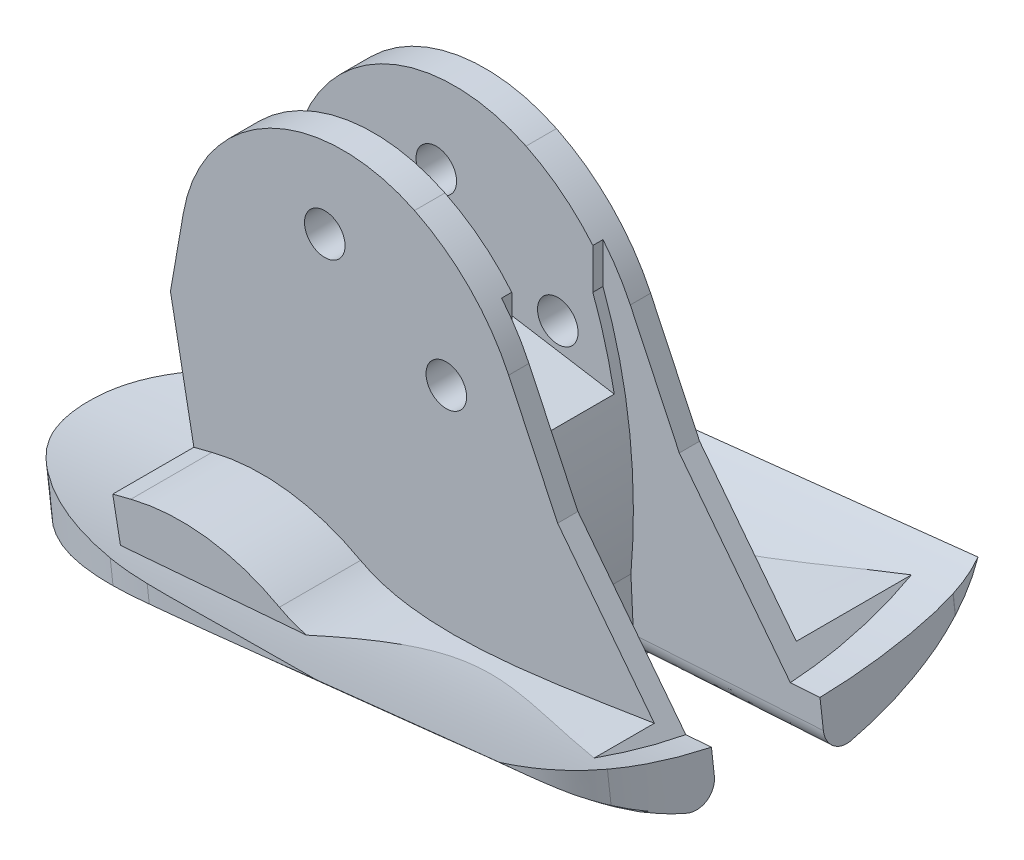
SolidWorks part; units mm, degrees
ref_plane "Спереди" through (0, 0, 0) normal (0, 0, 1) x (1, 0, 0)
ref_plane "Сверху" through (0, 0, 0) normal (0, 1, 0) x (1, 0, 0)
ref_plane "Справа" through (0, 0, 0) normal (1, 0, 0) x (0, 0, -1)
sketch "Sketch5" plane through (0, 0, 0) normal (0, 0, 1) x (1, 0, 0)
  line L0 (1.7523, 0.4742) -> (37.3029, 86.8114) construction
  line L1 (-1.0106, -0.6044) -> (29.6618, 87.5839) construction
  line L2 (0, 0) -> (17.8901, 43.1295)
  line L3 (0, 0) -> (114.3643, 0) construction
  line L4 (23.8823, 39.6684) -> (24.5035, 51.2503)
  line B0 (17.4507, 115.16) -> (29.9551, 112.6983)
  spline B1 degree 3 poles (29.9551, 112.6983) (28.321, 116.0983) (27.9284, 121.1676) (30.1713, 134.4746) (29.8473, 132.0116) (30.6222, 139.9349) (27.0176, 140.9027) knots 0 0 0 0 0.297085 0.369784 0.687298 1 1 1 1
  spline B2 degree 2 poles (27.0176, 140.9027) (20.5603, 128.6427) (17.4507, 115.16) knots 0 0 0 1 1 1
  spline B3 degree 2 poles (27.0176, 140.9027) (26.5004, 134.6878) (22.2537, 130.5645) knots 0 0 0 1 1 1
  line B4 (17.1977, 114.3508) -> (29.842, 112.2111)
  line B5 (28.7001, 84.8969) -> (10.3668, 87.513)
  spline B6 degree 1 poles (17.1977, 114.3508) (10.3668, 87.513) knots 0 0 1 1
  spline B7 degree 2 poles (29.842, 112.2111) (22.5534, 98.8452) (28.7001, 84.8969) knots 0 0 0 1 1 1
  line B8 (10.1904, 87.4159) -> (28.2572, 84.4958)
  line B9 (32.8909, 45.7292) -> (10.0695, 42.8593)
  spline B10 degree 2 poles (10.1904, 87.4159) (10.0234, 65.1379) (10.0695, 42.8593) knots 0 0 0 1 1 1
  spline B11 degree 2 poles (28.2572, 84.4958) (20.6417, 64.1094) (32.8909, 45.7292) knots 0 0 0 1 1 1
  line B12 (10.2797, 36.8758) -> (3.9253, -13.9853)
  line B13 (3.9253, -13.9853) -> (33.9594, -31.0804)
  line B14 (33.9594, -31.0804) -> (45.9193, -27.7969)
  line B15 (45.9193, -27.7969) -> (58.2918, -13.9853)
  line B16 (58.2918, -13.9853) -> (69.0331, -4.9875)
  line B17 (69.0331, -4.9875) -> (82.514, 2.0236)
  line B18 (82.514, 2.0236) -> (89.2736, 3.8794)
  line B19 (89.2736, 3.8794) -> (92.4846, 9.5208)
  line B20 (92.4846, 9.5208) -> (96.8914, 17.263)
  line B21 (96.8914, 17.263) -> (101.4978, 21.1217)
  line B22 (101.4978, 21.1217) -> (103.9241, 23.1541)
  line B23 (104.261, 27.4157) -> (104.5375, 25.5318)
  line B24 (84.192, 21.2056) -> (87.7484, 22.7822)
  line B25 (87.7484, 22.7822) -> (92.912, 27.4956)
  line B26 (71.6086, 15.6268) -> (84.192, 21.2056)
  line B27 (92.912, 27.4956) -> (95.357, 29.7274)
  line B28 (95.357, 29.7274) -> (96.8049, 29.9399)
  line B29 (71.6086, 15.6268) -> (53.4239, 15.2713)
  line B30 (48.0904, 17.5622) -> (39.9394, 26.4919)
  line B31 (39.9394, 26.4919) -> (33.9594, 37.99)
  line B32 (33.9594, 37.99) -> (10.2797, 36.8758)
  line B33 (96.8049, 29.9399) -> (99.4078, 30.2175)
  line B34 (99.4078, 30.2175) -> (102.2786, 29.261)
  line B35 (102.2786, 29.261) -> (104.261, 27.4157)
  line B36 (104.5375, 25.5318) -> (103.9241, 23.1541)
  arc B37 (53.4239, 15.2713) -> (48.0904, 17.5622) centre (53.2864, 22.3051) cw
  spline B38 degree 3 poles (104.261, 27.4157) (103.5289, 27.0494) (99.8378, 26.2685) (94.8982, 17.2338) (98.6516, 18.7375) knots 0 0 0 0 0.441207 1 1 1 1
  line B39 (27.7375, 116.5129) -> (14.1959, 87.8955)
  line B40 (27.7375, 116.5129) -> (25.9485, 114.8372)
  line B41 (25.9485, 114.8372) -> (27.5763, 114.067)
  line B42 (27.7375, 116.5129) -> (27.5763, 114.067)
  line B43 (26.1527, 88.0864) -> (17.8901, 43.1295)
  line B44 (19.3622, 85.005) -> (23.8823, 39.6684)
  line B45 (19.3622, 85.005) -> (17.7584, 73.9508)
  line B46 (17.7584, 73.9508) -> (23.117, 74.485)
  line B47 (23.117, 74.485) -> (19.3622, 85.005)
  line B48 (26.1527, 88.0864) -> (23.7481, 82.7635)
  line B49 (23.7481, 82.7635) -> (25.1278, 82.5099)
  line B50 (25.1278, 82.5099) -> (26.5087, 82.2561)
  line B51 (26.5087, 82.2561) -> (26.1527, 88.0864)
  line B52 (26.1527, 88.0864) -> (19.3622, 85.005)
  line B53 (19.3622, 85.005) -> (22.3683, 87.7853)
  line B54 (22.3683, 87.7853) -> (22.9012, 86.6109)
  line B55 (22.9012, 86.6109) -> (23.4998, 85.2917)
  line B56 (23.4998, 85.2917) -> (19.3622, 85.005)
  dimension "D1" = 93.37
  dimension "D2" = 93.37
  dimension "D4" = 67.471
  dimension "D5" = 8.764
sketch_block_instance "Block1-1"
sketch_block "Block1"
sketch_block_instance "Block2-1"
sketch_block "Block2"
sketch_block_instance "Block3-1"
sketch_block "Block3"
sketch_block_instance "Block18-1"
sketch_block "Block18"
sketch_block_instance "Block44-1"
sketch_block "Block44"
sketch_block_instance "Block46-1"
sketch_block "Block46"
sketch_block_instance "Block47-1"
sketch_block "Block47"
sketch_block_instance "Block48-1"
sketch_block "Block48"
sketch_block_instance "Block50-1"
sketch_block "Block50"
sketch "Sketch10" plane through (0, 0, 0) normal (0, 0, 1) x (1, 0, 0)
  line L0 (24.801, 46.2069) -> (29.3738, 36.5215)
  line L3 (29.3738, 36.5215) -> (36.9938, 26.6828)
  line L21 (10.2797, 36.8758) -> (12.7888, 23.6588)
  line L22 (12.7888, 23.6588) -> (36.9938, 26.6828)
  line L23 (10.2797, 36.8758) -> (12.3218, 48.6569)
  line L24 (12.3218, 48.6569) -> (24.801, 46.2069)
  circle A0 centre (17.8901, 43.1295) radius 1
  circle A2 centre (23.8823, 39.6684) radius 1
  dimension "D1" = 2
  dimension "D2" = 2
extrude "Boss-Extrude5" add sketch "Sketch10" along normal mid plane 15
sketch "Sketch11" plane through (0, 0, 7.5) normal (0, 0, 1) x (1, 0, 0)
  line L0 (17.8254, 32.4239) -> (9.1239, 30.2079)
  line L1 (37.7529, 30.846) -> (34.6935, 60.2717)
  line L2 (34.6935, 60.2717) -> (6.5943, 53.1599)
  line L3 (6.5943, 53.1599) -> (9.1239, 30.2079)
  line L4 (37.7529, 30.846) -> (30.6791, 30.1551) construction
  line L5 (30.6791, 30.1551) -> (19.269, 26.7342) construction
  line L6 (19.269, 26.7342) -> (17.8254, 32.4239) construction
  line L7 (12.3218, 48.6569) -> (10.2797, 36.8758) construction
  spline S1 degree 3 poles (37.7529, 30.846) (30.6791, 30.1551) (19.269, 26.7342) (17.8254, 32.4239) knots 0 0 0 0 1 1 1 1
extrude "Cut-Extrude1" cut sketch "Sketch11" against normal blind 4
fillet "Fillet1" radius 10 1 edges at (24.801, 46.2069, -2)
extrude "Cut-Extrude6" cut sketch "Sketch11<2>" against normal blind 10 from offset 11 offset against normal yes
sketch "Sketch11<2>" plane through (0, 0, 7.5) normal (0, 0, 1) x (1, 0, 0) same geometry as "Sketch11"
sketch "Sketch16" plane through (0, 0, 0) normal (0, 0, 1) x (1, 0, 0)
  line L1 (10.0743, 54.3608) -> (34.4186, 54.3608)
  line L2 (10.0743, 54.3608) -> (10.0743, 40.6451)
  line L3 (10.0743, 40.6451) -> (34.4186, 36.6644)
  line L4 (34.4186, 54.3608) -> (34.4186, 36.6644)
extrude "Cut-Extrude7" cut sketch "Sketch16" against normal mid plane 4
sketch "Sketch26" plane through (36.0406, 27.9136, 0) normal (0.7906, 0.6123, 0) x (0, 0, -1)
  line L15 (3.5, 10.8877) -> (-3.5, 10.8877)
  line L16 (-3.5, 10.8877) -> (-3.5, 3.0978)
  line L17 (-3.5, 3.0978) -> (-7.5, 3.0978)
  line L18 (-7.5, 3.0978) -> (-7.5, -1.5567)
  line L19 (-7.5, -1.5567) -> (7.5, -1.5567)
  line L20 (7.5, -1.5567) -> (7.5, 3.0978)
  line L21 (7.5, 3.0978) -> (3.5, 3.0978)
  line L22 (3.5, 3.0978) -> (3.5, 10.8877)
  line L27 (3.5, 10.8877) -> (-3.5, 10.8877)
  line L28 (-3.5, 10.8877) -> (-3.5, 3.0978)
  line L29 (-3.5, 3.0978) -> (-7.5, 3.0978)
  line L30 (-7.5, 3.0978) -> (-7.5, -1.5567)
  line L31 (-7.5, -1.5567) -> (7.5, -1.5567)
  line L32 (7.5, -1.5567) -> (7.5, 3.0978)
  line L33 (7.5, 3.0978) -> (3.5, 3.0978)
  line L34 (3.5, 3.0978) -> (3.5, 10.8877)
  dimension "D1" = 0
extrude "Boss-Extrude11" add sketch "Sketch26" along normal blind 9
sketch "Sketch28" plane through (0.9532, -1.2307, 0) normal (0.6123, -0.7906, 0) x (0.7906, 0.6123, 0)
  line L0 (38.2441, 4.6151) -> (38.2441, -4.6151) construction
  line L1 (54.5861, 0) -> (45.5861, 0) construction
  line L2 (54.5861, 7.5) -> (54.5861, -7.5) construction
  line L3 (45.5861, 7.5) -> (45.5861, -7.5) construction
  circle A0 centre (38.2441, 4.6151) radius 1
  circle A1 centre (38.2441, -4.6151) radius 1
  point P10 (38.2441, 0)
  dimension "D1" = 2
sketch "Sketch32" plane through (43.1561, 33.4245, 0) normal (0.7906, 0.6123, 0) x (0, 0, -1)
  line L16 (3.5, 10.8877) -> (-3.5, 10.8877)
  line L17 (-3.5, 10.8877) -> (-3.5, 3.0978)
  line L18 (-3.5, 3.0978) -> (-7.5, 3.0978)
  line L19 (-7.5, 3.0978) -> (-7.5, -1.5567)
  line L20 (-7.5, -1.5567) -> (7.5, -1.5567)
  line L21 (7.5, -1.5567) -> (7.5, 3.0978)
  line L22 (7.5, 3.0978) -> (3.5, 3.0978)
  line L23 (3.5, 3.0978) -> (3.5, 10.8877)
  line L28 (3.5, 10.8877) -> (-3.5, 10.8877)
  line L29 (-3.5, 10.8877) -> (-3.5, 3.0978)
  line L30 (-3.5, 3.0978) -> (-7.5, 3.0978)
  line L31 (-7.5, 3.0978) -> (-7.5, -1.5567)
  line L32 (-7.5, -1.5567) -> (7.5, -1.5567)
  line L33 (7.5, -1.5567) -> (7.5, 3.0978)
  line L34 (7.5, 3.0978) -> (3.5, 3.0978)
  line L35 (3.5, 3.0978) -> (3.5, 10.8877)
  dimension "D1" = 0
extrude "Cut-Extrude9" cut sketch "Sketch32" against normal blind 9
fillet "Fillet2" radius 8 2 edges at (12.3218, 48.6569, 2.75) (12.3218, 48.6569, -2.75)
fillet "Fillet3" radius 10 2 edges at (17.8254, 32.4239, 5.5) (17.8254, 32.4239, -5.5)
sketch "Sketch33" plane through (0, 0, -7.5) normal (0, 0, -1) x (-1, 0, 0)
  line L8 (-11.4338, 30.7962) -> (-12.3264, 31.0235)
  line L9 (-34.1438, 30.3627) -> (-36.9938, 26.6828)
  line L10 (-36.9938, 26.6828) -> (-12.7888, 23.6588)
  line L15 (-12.7888, 23.6588) -> (-11.4338, 30.7962)
  line L16 (-11.4338, 30.7962) -> (-12.3264, 31.0235)
  line L17 (-34.1438, 30.3627) -> (-36.9938, 26.6828)
  line L18 (-36.9938, 26.6828) -> (-12.7888, 23.6588)
  line L23 (-12.7888, 23.6588) -> (-11.4338, 30.7962)
  arc A1 (-12.3264, 31.0235) -> (-19.6523, 30.0735) centre (-14.7943, 21.3328) ccw
  arc A2 (-12.3264, 31.0235) -> (-19.6523, 30.0735) centre (-14.7943, 21.3328) ccw
  spline S1 degree 3 poles (-2248.4331, 2036.9035) (2398.5946, -1976.7775) (-2489.4145, 2007.6298) (2270.2063, -1890.107) knots -4.784793 -4.784793 -4.784793 -4.784793 6.243162 6.243162 6.243162 6.243162 only from (-19.6523, 30.0735) to (-34.1438, 30.3627)
  spline S2 degree 3 poles (-19.6523, 30.0735) (-22.7361, 28.3596) (-28.8813, 29.5444) (-34.1438, 30.3627) knots 0.191604 0.191604 0.191604 0.191604 0.842502 0.842502 0.842502 0.842502
  line M11 (-11.4338, 30.7962) -> (-12.3264, 31.0235)
  arc M12 (-12.3264, 31.0235) -> (-19.6523, 30.0735) centre (-14.7943, 21.3328) ccw
  spline M13 degree 3 poles (-37.7529, 30.846) (-30.6791, 30.1551) (-19.269, 26.7342) (-17.8254, 32.4239) knots 0 0 0 0 1 1 1 1 only from (-19.6523, 30.0735) to (-34.1438, 30.3627)
  line M14 (-34.1438, 30.3627) -> (-36.9938, 26.6828)
  line M15 (-36.9938, 26.6828) -> (-12.7888, 23.6588)
  line M19 (-36.9938, 26.6828) -> (-12.7888, 23.6588)
  line M20 (-12.7888, 23.6588) -> (-11.4338, 30.7962)
  dimension "D1" = 0
extrude "Boss-Extrude15" add sketch "Sketch33" along normal blind 2 contours M20 M11 M12 M13 M14 M15 M19 region at (22.1832, 27.576, -7.5)
ref_plane "Plane1" through (36.5972, 26.9065, -1.1603) normal (-0.9966, -0.0705, 0.0433) x (0.0432, 0.0031, 0.9991)
sketch "Sketch34" plane through (36.5972, 26.9065, -1.1603) normal (-0.9966, -0.0705, 0.0433) x (0.0432, 0.0031, 0.9991)
  line L0 (10.9628, 4.6222) -> (3.477, -2.4087) construction
  line L2 (3.477, -2.4087) -> (-3.5213, -0.2511) construction
  line L4 (-3.5213, -0.2511) -> (-6.924, 1.4367) construction
  line L5 (-6.924, 1.4367) -> (-9.806, 4.1457) construction
  line L6 (8.6686, -0.2511) -> (-8.3155, -0.2511) construction
  line L7 (10.9628, 4.6222) -> (5.1029, 2.7181) construction
  line L8 (5.1029, 2.7181) -> (1.0957, 2.098) construction
  line L9 (1.0957, 2.098) -> (-5.2968, 2.5273) construction
  line L10 (-5.2968, 2.5273) -> (-9.806, 4.1457) construction
  spline S0 degree 4 poles (10.9628, 4.6222) (3.477, -2.4087) (-3.5213, -0.2511) (-6.924, 1.4367) (-9.806, 4.1457) knots 0 0 0 0 0 1 1 1 1 1
  spline S1 degree 4 poles (10.9628, 4.6222) (5.1029, 2.7181) (1.0957, 2.098) (-5.2968, 2.5273) (-9.806, 4.1457) knots 0 0 0 0 0 1 1 1 1 1
extrude "Boss-Extrude16" add sketch "Sketch34" along normal blind 50 and the other way blind 10
sketch "Sketch35" plane through (-2.7138, 21.7221, 0) normal (0.124, -0.9923, 0) x (0.9923, 0.124, 0)
  line L2 (39.6124, -9.2736) -> (39.614, -9.2589)
  circle A0 centre (27.3927, -0.6279) radius 55.4026
  spline S32 degree 3 poles (24.9565, -10.7059) (25.5212, -10.8521) (26.0851, -10.9988) (27.2128, -11.2896) (27.7763, -11.4341) (28.3423, -11.5719) knots 0 0 0 0 0.5 0.5 1 1 1 1
  spline S33 degree 3 poles (19.0873, -9.1591) (20.0581, -9.4433) (21.0399, -9.6954) (22.9999, -10.202) (23.9795, -10.4528) (24.9565, -10.7059) knots 0 0 0 0 0.5 0.5 1 1 1 1
  spline S34 degree 3 poles (15.2528, -7.7133) (15.8688, -8.0055) (16.4922, -8.2786) (17.7718, -8.7565) (18.4259, -8.9655) (19.0873, -9.1591) knots 0 0 0 0 0.5 0.5 1 1 1 1
  spline S35 degree 3 poles (8.1536, -3.0322) (8.4043, -3.2912) (8.6672, -3.5343) (9.2066, -4.0025) (9.4833, -4.227) (10.3296, -4.879) (10.9159, -5.2857) (12.1173, -6.0499) (12.7309, -6.4082) (13.9786, -7.0877) (14.6116, -7.4091) (15.2528, -7.7133) knots 0 0 0 0 0.125 0.125 0.25 0.25 0.5 0.5 0.75 0.75 1 1 1 1
  spline S36 degree 3 poles (6.8672, -1.0785) (6.9335, -1.2667) (7.0135, -1.4502) (7.1946, -1.8009) (7.2957, -1.9686) (7.6253, -2.4524) (7.8798, -2.7495) (8.1536, -3.0322) knots 0 0 0 0 0.25 0.25 0.5 0.5 1 1 1 1
  spline S37 degree 3 poles (7.0947, 2.5911) (6.9606, 2.3051) (6.8532, 2.0075) (6.6972, 1.4025) (6.6472, 1.0933) (6.6049, 0.4613) (6.614, 0.1448) (6.692, -0.4743) (6.7617, -0.7791) (6.8672, -1.0785) knots 0 0 0 0 0.25 0.25 0.5 0.5 0.75 0.75 1 1 1 1
  spline S38 degree 3 poles (8.5033, 4.4734) (8.2174, 4.1997) (7.9498, 3.9116) (7.4739, 3.2892) (7.2653, 2.9551) (7.0947, 2.5911) knots 0 0 0 0 0.5 0.5 1 1 1 1
  spline S39 degree 3 poles (15.981, 8.6546) (15.2904, 8.4399) (14.6155, 8.1883) (13.2929, 7.6281) (12.645, 7.3153) (11.3861, 6.6266) (10.7736, 6.2482) (9.89, 5.6274) (9.6016, 5.4119) (9.0397, 4.9603) (8.7657, 4.7246) (8.5033, 4.4734) knots 0 0 0 0 0.25 0.25 0.5 0.5 0.75 0.75 0.875 0.875 1 1 1 1
  spline S40 degree 3 poles (18.362, 9.1871) (17.9562, 9.1266) (17.5535, 9.0566) (16.7592, 8.8815) (16.3681, 8.7749) (15.981, 8.6546) knots 0 0 0 0 0.5 0.5 1 1 1 1
  spline S41 degree 3 poles (29.3353, 10.4123) (28.4207, 10.3194) (27.5084, 10.2133) (25.6823, 10.0027) (24.7686, 9.8978) (22.9384, 9.699) (22.0218, 9.6059) (20.647, 9.4639) (20.1887, 9.4158) (19.2736, 9.3113) (18.8167, 9.2551) (18.362, 9.1871) knots 0 0 0 0 0.25 0.25 0.5 0.5 0.75 0.75 0.875 0.875 1 1 1 1
  spline S42 degree 3 poles (38.6158, 6.7752) (38.4879, 7.1918) (38.3336, 7.5867) (37.9581, 8.3332) (37.7427, 8.6893) (37.3485, 9.165) (37.2045, 9.3143) (36.8928, 9.5962) (36.7245, 9.7296) (36.3583, 9.974) (36.1635, 10.0827) (35.7443, 10.269) (35.5168, 10.3471) (35.0463, 10.4694) (34.8043, 10.5144) (34.311, 10.582) (34.0586, 10.6045) (33.3074, 10.6477) (32.8089, 10.6463) (31.8139, 10.6152) (31.3175, 10.5849) (30.3258, 10.5087) (29.8304, 10.4626) (29.3353, 10.4123) knots 0 0 0 0 0.125 0.125 0.25 0.25 0.3125 0.3125 0.375 0.375 0.4375 0.4375 0.5 0.5 0.5625 0.5625 0.625 0.625 0.75 0.75 0.875 0.875 1 1 1 1
  spline S43 degree 3 poles (39.614, -9.2589) (39.6788, -8.6788) (39.7035, -8.0722) (39.7298, -6.8066) (39.7311, -6.1432) (39.7281, -4.7965) (39.7222, -4.1108) (39.7072, -3.0634) (39.701, -2.7112) (39.6835, -2.0003) (39.6718, -1.6404) (39.6244, -0.5691) (39.5786, 0.1385) (39.4668, 1.5416) (39.4008, 2.239) (39.2432, 3.6136) (39.1532, 4.2784) (38.93, 5.5624) (38.7979, 6.1818) (38.6158, 6.7752) knots 0 0 0 0 0.125 0.125 0.25 0.25 0.375 0.375 0.4375 0.4375 0.5 0.5 0.625 0.625 0.75 0.75 0.875 0.875 1 1 1 1
  spline S44 degree 3 poles (38.1236, -12.3487) (38.2624, -12.2667) (38.3838, -12.1721) (38.6007, -11.9688) (38.6957, -11.8604) (38.9537, -11.5192) (39.0907, -11.2681) (39.3113, -10.7408) (39.3963, -10.4645) (39.4986, -10.0321) (39.5255, -9.8845) (39.5737, -9.5834) (39.5946, -9.43) (39.6124, -9.2736) knots 0 0 0 0 0.125 0.125 0.25 0.25 0.5 0.5 0.75 0.75 0.875 0.875 1 1 1 1
  spline S45 degree 3 poles (37.8947, -12.4638) (37.9761, -12.4297) (38.0519, -12.391) (38.1236, -12.3487) knots 0 0 0 0 1 1 1 1
  spline S46 degree 3 poles (34.5417, -12.5645) (34.828, -12.587) (35.1142, -12.6076) (35.6868, -12.6412) (35.9731, -12.6544) (36.5456, -12.6643) (36.8315, -12.6617) (37.2498, -12.6244) (37.389, -12.6058) (37.6533, -12.5499) (37.7782, -12.5125) (37.8947, -12.4638) knots 0 0 0 0 0.25 0.25 0.5 0.5 0.75 0.75 0.875 0.875 1 1 1 1
  spline S47 degree 3 poles (28.3423, -11.5719) (29.3519, -11.8178) (30.3705, -12.041) (32.442, -12.3728) (33.4913, -12.4819) (34.5417, -12.5645) knots 0 0 0 0 0.5 0.5 1 1 1 1
extrude "Cut-Extrude10" cut sketch "Sketch35" against normal blind 30 and the other way blind 72
sketch "Sketch36" plane through (36.5972, 26.9065, -1.1603) normal (-0.9966, -0.0705, 0.0433) x (0.0432, 0.0031, 0.9991)
  line L1 (-11.6294, 6.1274) -> (-6.4307, -1.0001) construction
  line L2 (-6.4307, -1.0001) -> (3.088, -1.7462) construction
  line L3 (3.088, -1.7462) -> (7.2256, 0.8941) construction
  line L5 (7.2256, 0.8941) -> (11.8416, 5.5345) construction
  line L6 (-11.6294, 6.1274) -> (-10.8368, -5.0459)
  line L7 (-10.8368, -5.0459) -> (4.6769, -6.7725)
  line L8 (4.6769, -6.7725) -> (13.0264, -2.4689)
  line L9 (13.0264, -2.4689) -> (11.8416, 5.5345)
  spline S0 degree 4 poles (-11.6294, 6.1274) (-6.4307, -1.0001) (3.088, -1.7462) (7.2256, 0.8941) (11.8416, 5.5345) knots 0 0 0 0 0 1 1 1 1 1
extrude "Cut-Extrude11" cut sketch "Sketch36" along normal blind 35 and the other way blind 10
sketch "Sketch37" plane through (0, 0, 0) normal (0, 1, 0) x (1, 0, 0)
  circle A0 centre (31.576, 4.5788) radius 1.0332
  circle A1 centre (31.576, -4.6483) radius 1.025
sketch "Sketch38" plane through (0, 0, 0) normal (0, 0, 1) x (1, 0, 0)
  line L0 (25.6108, 47.7844) -> (25.6108, 41.7534)
  line L1 (26.9876, 30.1593) -> (27.4181, 21.425)
  line L2 (27.4181, 21.425) -> (39.9211, 21.425)
  line L3 (39.9211, 21.425) -> (37.073, 47.7844)
  line L4 (37.073, 47.7844) -> (25.6108, 47.7844)
  line L6 (25.6108, 41.7534) -> (27.5342, 36.6066) construction
  line L7 (27.5342, 36.6066) -> (26.9876, 30.1593) construction
  spline S0 degree 2 poles (25.6108, 41.7534) (27.5342, 36.6066) (26.9876, 30.1593) knots 0 0 0 1 1 1
extrude "Cut-Extrude13" cut sketch "Sketch38" against normal mid plane 5
fillet "Fillet4" radius 1 2 edges
ref_plane "Plane2" through (18.7826, 29.7777, 0) normal (0.5335, 0.8458, 0) x (0.8458, -0.5335, 0)
sketch "Sketch39" plane through (18.7826, 29.7777, 0) normal (0.5335, 0.8458, 0) x (0.8458, -0.5335, 0)
  line L0 (-3.4633, 5) -> (1.5367, 5) construction
  line L1 (-3.4633, 5) -> (1.5367, 5) construction
  line L2 (-3.4633, 6.5) -> (1.5367, 6.5)
  line L3 (-3.4633, 3.5) -> (1.5367, 3.5)
  arc A0 (-3.4633, 6.5) -> (-3.4633, 3.5) centre (-3.4633, 5) ccw
  arc A1 (1.5367, 3.5) -> (1.5367, 6.5) centre (1.5367, 5) ccw
  point P2 (-0.9633, 5)
  dimension "D1" = 3
extrude "Cut-Extrude14" cut sketch "Sketch39" against normal blind 10 and the other way blind 10
